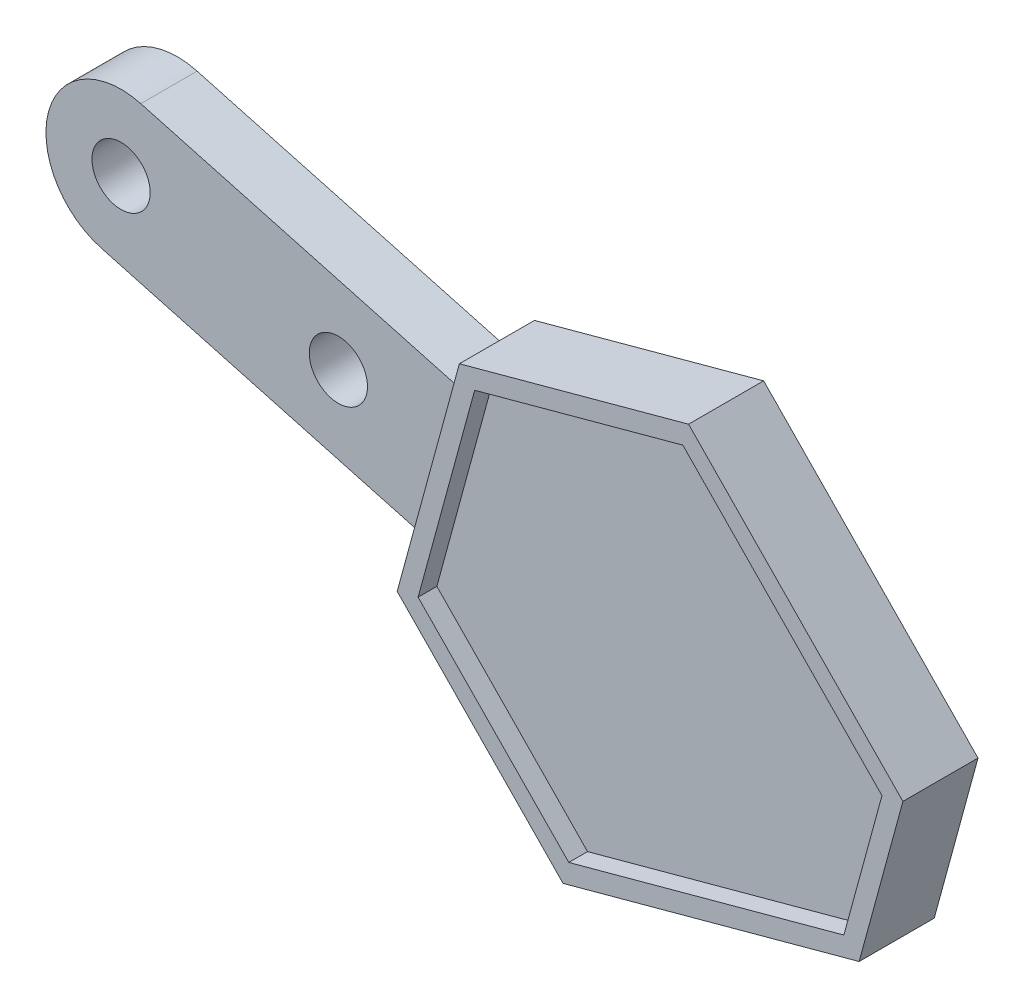
SolidWorks part; units mm, degrees
ref_plane "Front Plane" through (0, 0, 0) normal (0, 0, 1) x (1, 0, 0)
ref_plane "Top Plane" through (0, 0, 0) normal (0, 1, 0) x (1, 0, 0)
ref_plane "Right Plane" through (0, 0, 0) normal (1, 0, 0) x (0, 0, -1)
sketch "Sketch1" plane through (0, 0, 0) normal (0, 0, 1) x (1, 0, 0)
  line L0 (5.668, 49.272) -> (24.9641, 44.0125) construction
  line L1 (5.668, 49.272) -> (24.9641, 44.0125)
  line L2 (6.194, 51.2016) -> (4.6162, 45.4127) construction
  line L3 (6.194, 51.2016) -> (4.6162, 45.4127)
  line L4 (4.0197, 43.2246) -> (3.9784, 43.2827)
  line L5 (7.4235, 40.5016) -> (24.7899, 35.7682)
  line L6 (24.9641, 44.0125) -> (26.8937, 43.4866)
  line L7 (26.8937, 43.4866) -> (24.7899, 35.7682)
  line L8 (25.8418, 39.6274) -> (49.9619, 33.0531) construction
  line L9 (24.7899, 35.7682) -> (24.1848, 33.5479)
  line L10 (24.1848, 33.5479) -> (33.0227, 24.4939)
  line L11 (51.1276, 37.3298) -> (48.7962, 28.7764)
  line L12 (48.7962, 28.7764) -> (33.0227, 24.4939)
  line L13 (26.8937, 43.4866) -> (27.4989, 45.7068)
  line L14 (27.4989, 45.7068) -> (39.7088, 49.0239)
  line L15 (51.1276, 37.3298) -> (39.7088, 49.0239)
  arc A0 (4.6162, 45.4127) -> (7.4235, 40.5016) centre (8.4754, 44.3609) ccw construction
  arc A1 (4.6162, 45.4127) -> (7.4235, 40.5016) centre (8.4754, 44.3609) ccw
  dimension "D1" = 18
  dimension "D2" = 25
extrude "Boss-Extrude1" add sketch "Sketch1" along normal blind 3 contours L8 L7 L9 L10 L12 L11 | L7 L8 L11 L15 L14 L13 | L3 A1 L5 L7 L6 L1 region at (15.4393, 42.5268, 0) region at (38.5306, 41.1072, 0) region at (36.0247, 31.9135, 0)
fillet "Fillet1" radius 4 1 edges at (5.668, 49.272, 1.5)
sketch "Sketch2" plane through (0, 0, 3) normal (0, 0, 1) x (1, 0, 0)
  line L28 (27.8585, 43.2236) -> (25.7547, 35.5052)
  line L29 (48.7962, 28.7764) -> (33.0227, 24.4939) construction
  line L30 (24.7899, 35.7682) -> (24.1848, 33.5479) construction
  line L31 (24.1848, 33.5479) -> (33.0227, 24.4939) construction
  line L32 (27.4989, 45.7068) -> (26.8937, 43.4866) construction
  line L33 (27.4989, 45.7068) -> (39.7088, 49.0239) construction
  line L34 (51.1276, 37.3298) -> (48.7962, 28.7764) construction
  line L35 (47.9819, 29.5915) -> (50.0123, 37.0406)
  line L36 (50.0123, 37.0406) -> (39.4038, 47.9048)
  line L37 (39.4038, 47.9048) -> (28.3132, 44.8918)
  line L38 (28.3132, 44.8918) -> (27.8585, 43.2236)
  line L39 (25.7547, 35.5052) -> (25.3001, 33.837)
  line L40 (25.3001, 33.837) -> (33.3278, 25.6129)
  line L41 (33.3278, 25.6129) -> (47.9819, 29.5915)
  line L42 (47.9819, 29.5915) -> (50.0123, 37.0406)
  line L43 (50.0123, 37.0406) -> (39.4038, 47.9048)
  line L44 (39.4038, 47.9048) -> (28.3132, 44.8918)
  line L45 (28.3132, 44.8918) -> (27.8585, 43.2236)
  line L46 (25.7547, 35.5052) -> (25.3001, 33.837)
  line L47 (25.3001, 33.837) -> (33.3278, 25.6129)
  line L48 (33.3278, 25.6129) -> (47.9819, 29.5915)
  line L49 (51.1276, 37.3298) -> (39.7088, 49.0239) construction
  line L50 (48.7962, 28.7764) -> (33.0227, 24.4939)
  line L51 (24.7899, 35.7682) -> (24.1848, 33.5479)
  line L52 (24.1848, 33.5479) -> (33.0227, 24.4939)
  line L53 (27.4989, 45.7068) -> (26.8937, 43.4866)
  line L54 (27.4989, 45.7068) -> (39.7088, 49.0239)
  line L55 (51.1276, 37.3298) -> (48.7962, 28.7764)
  line L56 (51.1276, 37.3298) -> (39.7088, 49.0239)
  line L57 (26.8937, 43.4866) -> (24.7899, 35.7682)
  dimension "D1" = 1
extrude "Boss-Extrude2" add sketch "Sketch2" along normal blind 1
sketch "Sketch5" plane through (0, 0, 3) normal (0, 0, 1) x (1, 0, 0)
  circle A0 centre (8.4754, 44.3609) radius 1.55
  circle A1 centre (20.053, 41.2052) radius 1.55 construction
  circle A2 centre (20.053, 41.2052) radius 1.55
  dimension "D1" = 3.1
extrude "Cut-Extrude1" cut sketch "Sketch5" against normal up to next
